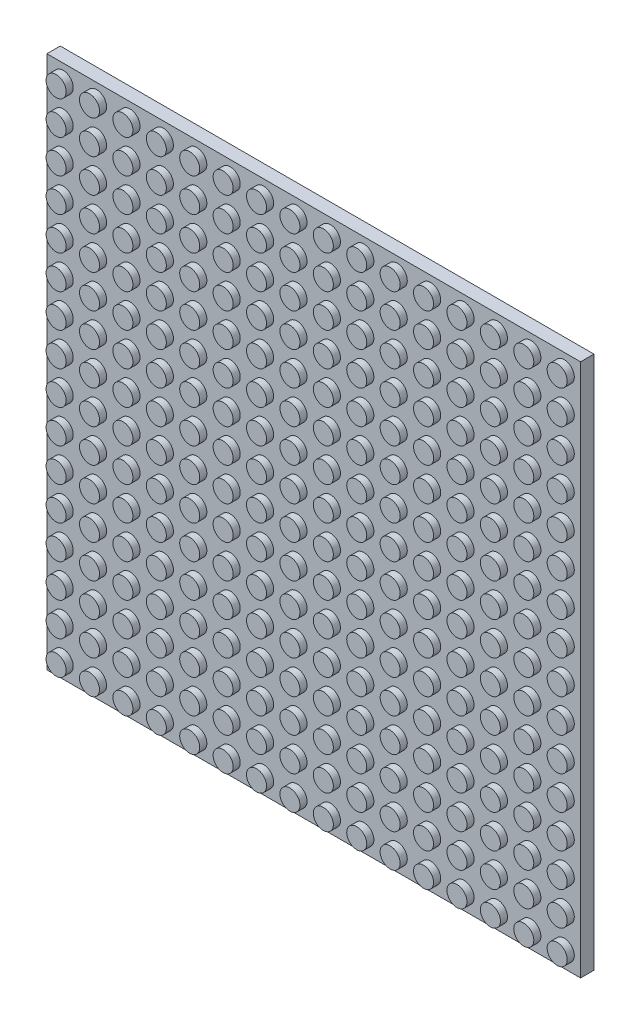
SolidWorks part; units mm, degrees
ref_plane "Спереди" through (0, 0, 0) normal (0, 0, 1) x (1, 0, 0)
ref_plane "Сверху" through (0, 0, 0) normal (0, 1, 0) x (1, 0, 0)
ref_plane "Справа" through (0, 0, 0) normal (1, 0, 0) x (0, 0, -1)
sketch "Эскиз1" plane through (0, 0, 0) normal (0, 0, 1) x (1, 0, 0)
  line L1 (-63.9, -63.9) -> (63.9, -63.9)
  line L2 (-63.9, -63.9) -> (-63.9, 63.9)
  line L3 (-63.9, 63.9) -> (63.9, 63.9)
  line L4 (63.9, -63.9) -> (63.9, 63.9)
  line L5 (-63.9, -63.9) -> (63.9, 63.9) construction
  line L6 (-63.9, 63.9) -> (63.9, -63.9) construction
  point P0 (0, 0)
  dimension "D1" = 127.8
  dimension "D2" = 127.8
extrude "Бобышка-Вытянуть1" add sketch "Эскиз1" along normal blind 3.2
sketch "Эскиз2" plane through (0, 0, 3.2) normal (0, 0, 1) x (1, 0, 0)
  line L0 (-63.9, 63.9) -> (-63.9, -63.9) construction
  line L1 (63.9, 63.9) -> (-63.9, 63.9) construction
  circle A0 centre (-60, 60) radius 2.4
  circle A1 centre (-52, 60) radius 2.4
  circle A2 centre (-44, 60) radius 2.4
  circle A3 centre (-36, 60) radius 2.4
  circle A4 centre (-28, 60) radius 2.4
  circle A5 centre (-20, 60) radius 2.4
  circle A6 centre (-12, 60) radius 2.4
  circle A7 centre (-4, 60) radius 2.4
  circle A8 centre (4, 60) radius 2.4
  circle A9 centre (12, 60) radius 2.4
  circle A10 centre (20, 60) radius 2.4
  circle A11 centre (28, 60) radius 2.4
  circle A12 centre (36, 60) radius 2.4
  circle A13 centre (44, 60) radius 2.4
  circle A14 centre (52, 60) radius 2.4
  circle A15 centre (60, 60) radius 2.4
  circle A16 centre (-52, 52) radius 2.4
  circle A17 centre (-44, 52) radius 2.4
  circle A18 centre (-36, 52) radius 2.4
  circle A19 centre (-28, 52) radius 2.4
  circle A20 centre (-20, 52) radius 2.4
  circle A21 centre (-12, 52) radius 2.4
  circle A22 centre (-4, 52) radius 2.4
  circle A23 centre (4, 52) radius 2.4
  circle A24 centre (12, 52) radius 2.4
  circle A25 centre (20, 52) radius 2.4
  circle A26 centre (28, 52) radius 2.4
  circle A27 centre (36, 52) radius 2.4
  circle A28 centre (44, 52) radius 2.4
  circle A29 centre (52, 52) radius 2.4
  circle A30 centre (60, 52) radius 2.4
  circle A31 centre (-52, 44) radius 2.4
  circle A32 centre (-44, 44) radius 2.4
  circle A33 centre (-36, 44) radius 2.4
  circle A34 centre (-28, 44) radius 2.4
  circle A35 centre (-20, 44) radius 2.4
  circle A36 centre (-12, 44) radius 2.4
  circle A37 centre (-4, 44) radius 2.4
  circle A38 centre (4, 44) radius 2.4
  circle A39 centre (12, 44) radius 2.4
  circle A40 centre (20, 44) radius 2.4
  circle A41 centre (28, 44) radius 2.4
  circle A42 centre (36, 44) radius 2.4
  circle A43 centre (44, 44) radius 2.4
  circle A44 centre (52, 44) radius 2.4
  circle A45 centre (60, 44) radius 2.4
  circle A46 centre (-52, 36) radius 2.4
  circle A47 centre (-44, 36) radius 2.4
  circle A48 centre (-36, 36) radius 2.4
  circle A49 centre (-28, 36) radius 2.4
  circle A50 centre (-20, 36) radius 2.4
  circle A51 centre (-12, 36) radius 2.4
  circle A52 centre (-4, 36) radius 2.4
  circle A53 centre (4, 36) radius 2.4
  circle A54 centre (12, 36) radius 2.4
  circle A55 centre (20, 36) radius 2.4
  circle A56 centre (28, 36) radius 2.4
  circle A57 centre (36, 36) radius 2.4
  circle A58 centre (44, 36) radius 2.4
  circle A59 centre (52, 36) radius 2.4
  circle A60 centre (60, 36) radius 2.4
  circle A61 centre (-52, 28) radius 2.4
  circle A62 centre (-44, 28) radius 2.4
  circle A63 centre (-36, 28) radius 2.4
  circle A64 centre (-28, 28) radius 2.4
  circle A65 centre (-20, 28) radius 2.4
  circle A66 centre (-12, 28) radius 2.4
  circle A67 centre (-4, 28) radius 2.4
  circle A68 centre (4, 28) radius 2.4
  circle A69 centre (12, 28) radius 2.4
  circle A70 centre (20, 28) radius 2.4
  circle A71 centre (28, 28) radius 2.4
  circle A72 centre (36, 28) radius 2.4
  circle A73 centre (44, 28) radius 2.4
  circle A74 centre (52, 28) radius 2.4
  circle A75 centre (60, 28) radius 2.4
  circle A76 centre (-52, 20) radius 2.4
  circle A77 centre (-44, 20) radius 2.4
  circle A78 centre (-36, 20) radius 2.4
  circle A79 centre (-28, 20) radius 2.4
  circle A80 centre (-20, 20) radius 2.4
  circle A81 centre (-12, 20) radius 2.4
  circle A82 centre (-4, 20) radius 2.4
  circle A83 centre (4, 20) radius 2.4
  circle A84 centre (12, 20) radius 2.4
  circle A85 centre (20, 20) radius 2.4
  circle A86 centre (28, 20) radius 2.4
  circle A87 centre (36, 20) radius 2.4
  circle A88 centre (44, 20) radius 2.4
  circle A89 centre (52, 20) radius 2.4
  circle A90 centre (60, 20) radius 2.4
  circle A91 centre (-52, 12) radius 2.4
  circle A92 centre (-44, 12) radius 2.4
  circle A93 centre (-36, 12) radius 2.4
  circle A94 centre (-28, 12) radius 2.4
  circle A95 centre (-20, 12) radius 2.4
  circle A96 centre (-12, 12) radius 2.4
  circle A97 centre (-4, 12) radius 2.4
  circle A98 centre (4, 12) radius 2.4
  circle A99 centre (12, 12) radius 2.4
  circle A100 centre (20, 12) radius 2.4
  circle A101 centre (28, 12) radius 2.4
  circle A102 centre (36, 12) radius 2.4
  circle A103 centre (44, 12) radius 2.4
  circle A104 centre (52, 12) radius 2.4
  circle A105 centre (60, 12) radius 2.4
  circle A106 centre (-52, 4) radius 2.4
  circle A107 centre (-44, 4) radius 2.4
  circle A108 centre (-36, 4) radius 2.4
  circle A109 centre (-28, 4) radius 2.4
  circle A110 centre (-20, 4) radius 2.4
  circle A111 centre (-12, 4) radius 2.4
  circle A112 centre (-4, 4) radius 2.4
  circle A113 centre (4, 4) radius 2.4
  circle A114 centre (12, 4) radius 2.4
  circle A115 centre (20, 4) radius 2.4
  circle A116 centre (28, 4) radius 2.4
  circle A117 centre (36, 4) radius 2.4
  circle A118 centre (44, 4) radius 2.4
  circle A119 centre (52, 4) radius 2.4
  circle A120 centre (60, 4) radius 2.4
  circle A121 centre (-52, -4) radius 2.4
  circle A122 centre (-44, -4) radius 2.4
  circle A123 centre (-36, -4) radius 2.4
  circle A124 centre (-28, -4) radius 2.4
  circle A125 centre (-20, -4) radius 2.4
  circle A126 centre (-12, -4) radius 2.4
  circle A127 centre (-4, -4) radius 2.4
  circle A128 centre (4, -4) radius 2.4
  circle A129 centre (12, -4) radius 2.4
  circle A130 centre (20, -4) radius 2.4
  circle A131 centre (28, -4) radius 2.4
  circle A132 centre (36, -4) radius 2.4
  circle A133 centre (44, -4) radius 2.4
  circle A134 centre (52, -4) radius 2.4
  circle A135 centre (60, -4) radius 2.4
  circle A136 centre (-52, -12) radius 2.4
  circle A137 centre (-44, -12) radius 2.4
  circle A138 centre (-36, -12) radius 2.4
  circle A139 centre (-28, -12) radius 2.4
  circle A140 centre (-20, -12) radius 2.4
  circle A141 centre (-12, -12) radius 2.4
  circle A142 centre (-4, -12) radius 2.4
  circle A143 centre (4, -12) radius 2.4
  circle A144 centre (12, -12) radius 2.4
  circle A145 centre (20, -12) radius 2.4
  circle A146 centre (28, -12) radius 2.4
  circle A147 centre (36, -12) radius 2.4
  circle A148 centre (44, -12) radius 2.4
  circle A149 centre (52, -12) radius 2.4
  circle A150 centre (60, -12) radius 2.4
  circle A151 centre (-52, -20) radius 2.4
  circle A152 centre (-44, -20) radius 2.4
  circle A153 centre (-36, -20) radius 2.4
  circle A154 centre (-28, -20) radius 2.4
  circle A155 centre (-20, -20) radius 2.4
  circle A156 centre (-12, -20) radius 2.4
  circle A157 centre (-4, -20) radius 2.4
  circle A158 centre (4, -20) radius 2.4
  circle A159 centre (12, -20) radius 2.4
  circle A160 centre (20, -20) radius 2.4
  circle A161 centre (28, -20) radius 2.4
  circle A162 centre (36, -20) radius 2.4
  circle A163 centre (44, -20) radius 2.4
  circle A164 centre (52, -20) radius 2.4
  circle A165 centre (60, -20) radius 2.4
  circle A166 centre (-52, -28) radius 2.4
  circle A167 centre (-44, -28) radius 2.4
  circle A168 centre (-36, -28) radius 2.4
  circle A169 centre (-28, -28) radius 2.4
  circle A170 centre (-20, -28) radius 2.4
  circle A171 centre (-12, -28) radius 2.4
  circle A172 centre (-4, -28) radius 2.4
  circle A173 centre (4, -28) radius 2.4
  circle A174 centre (12, -28) radius 2.4
  circle A175 centre (20, -28) radius 2.4
  circle A176 centre (28, -28) radius 2.4
  circle A177 centre (36, -28) radius 2.4
  circle A178 centre (44, -28) radius 2.4
  circle A179 centre (52, -28) radius 2.4
  circle A180 centre (60, -28) radius 2.4
  circle A181 centre (-52, -36) radius 2.4
  circle A182 centre (-44, -36) radius 2.4
  circle A183 centre (-36, -36) radius 2.4
  circle A184 centre (-28, -36) radius 2.4
  circle A185 centre (-20, -36) radius 2.4
  circle A186 centre (-12, -36) radius 2.4
  circle A187 centre (-4, -36) radius 2.4
  circle A188 centre (4, -36) radius 2.4
  circle A189 centre (12, -36) radius 2.4
  circle A190 centre (20, -36) radius 2.4
  circle A191 centre (28, -36) radius 2.4
  circle A192 centre (36, -36) radius 2.4
  circle A193 centre (44, -36) radius 2.4
  circle A194 centre (52, -36) radius 2.4
  circle A195 centre (60, -36) radius 2.4
  circle A196 centre (-52, -44) radius 2.4
  circle A197 centre (-44, -44) radius 2.4
  circle A198 centre (-36, -44) radius 2.4
  circle A199 centre (-28, -44) radius 2.4
  circle A200 centre (-20, -44) radius 2.4
  circle A201 centre (-12, -44) radius 2.4
  circle A202 centre (-4, -44) radius 2.4
  circle A203 centre (4, -44) radius 2.4
  circle A204 centre (12, -44) radius 2.4
  circle A205 centre (20, -44) radius 2.4
  circle A206 centre (28, -44) radius 2.4
  circle A207 centre (36, -44) radius 2.4
  circle A208 centre (44, -44) radius 2.4
  circle A209 centre (52, -44) radius 2.4
  circle A210 centre (60, -44) radius 2.4
  circle A211 centre (-52, -52) radius 2.4
  circle A212 centre (-44, -52) radius 2.4
  circle A213 centre (-36, -52) radius 2.4
  circle A214 centre (-28, -52) radius 2.4
  circle A215 centre (-20, -52) radius 2.4
  circle A216 centre (-12, -52) radius 2.4
  circle A217 centre (-4, -52) radius 2.4
  circle A218 centre (4, -52) radius 2.4
  circle A219 centre (12, -52) radius 2.4
  circle A220 centre (20, -52) radius 2.4
  circle A221 centre (28, -52) radius 2.4
  circle A222 centre (36, -52) radius 2.4
  circle A223 centre (44, -52) radius 2.4
  circle A224 centre (52, -52) radius 2.4
  circle A225 centre (60, -52) radius 2.4
  circle A226 centre (-52, -60) radius 2.4
  circle A227 centre (-44, -60) radius 2.4
  circle A228 centre (-36, -60) radius 2.4
  circle A229 centre (-28, -60) radius 2.4
  circle A230 centre (-20, -60) radius 2.4
  circle A231 centre (-12, -60) radius 2.4
  circle A232 centre (-4, -60) radius 2.4
  circle A233 centre (4, -60) radius 2.4
  circle A234 centre (12, -60) radius 2.4
  circle A235 centre (20, -60) radius 2.4
  circle A236 centre (28, -60) radius 2.4
  circle A237 centre (36, -60) radius 2.4
  circle A238 centre (44, -60) radius 2.4
  circle A239 centre (52, -60) radius 2.4
  circle A240 centre (60, -60) radius 2.4
  circle A241 centre (-60, 52) radius 2.4
  circle A242 centre (-60, 44) radius 2.4
  circle A243 centre (-60, 36) radius 2.4
  circle A244 centre (-60, 28) radius 2.4
  circle A245 centre (-60, 20) radius 2.4
  circle A246 centre (-60, 12) radius 2.4
  circle A247 centre (-60, 4) radius 2.4
  circle A248 centre (-60, -4) radius 2.4
  circle A249 centre (-60, -12) radius 2.4
  circle A250 centre (-60, -20) radius 2.4
  circle A251 centre (-60, -28) radius 2.4
  circle A252 centre (-60, -36) radius 2.4
  circle A253 centre (-60, -44) radius 2.4
  circle A254 centre (-60, -52) radius 2.4
  circle A255 centre (-60, -60) radius 2.4
  dimension "D1" = 3.9
  dimension "D2" = 3.9
  dimension "D3" = 16
extrude "Бобышка-Вытянуть2" add sketch "Эскиз2" along normal blind 1.7
sketch "Эскиз5" plane through (0, 0, 0) normal (0, 0, -1) x (-1, 0, 0)
  line L0 (-63.9, 63.9) -> (63.9, 63.9) construction
  line L1 (-63.9, -63.9) -> (-63.9, 63.9) construction
  circle A0 centre (-60, 60) radius 2.5
  circle A1 centre (-52, 60) radius 2.5
  circle A2 centre (-44, 60) radius 2.5
  circle A3 centre (-36, 60) radius 2.5
  circle A4 centre (-28, 60) radius 2.5
  circle A5 centre (-20, 60) radius 2.5
  circle A6 centre (-12, 60) radius 2.5
  circle A7 centre (-4, 60) radius 2.5
  circle A8 centre (4, 60) radius 2.5
  circle A9 centre (12, 60) radius 2.5
  circle A10 centre (20, 60) radius 2.5
  circle A11 centre (28, 60) radius 2.5
  circle A12 centre (36, 60) radius 2.5
  circle A13 centre (44, 60) radius 2.5
  circle A14 centre (52, 60) radius 2.5
  circle A15 centre (60, 60) radius 2.5
  circle A16 centre (-52, 52) radius 2.5
  circle A17 centre (-44, 52) radius 2.5
  circle A18 centre (-36, 52) radius 2.5
  circle A19 centre (-28, 52) radius 2.5
  circle A20 centre (-20, 52) radius 2.5
  circle A21 centre (-12, 52) radius 2.5
  circle A22 centre (-4, 52) radius 2.5
  circle A23 centre (4, 52) radius 2.5
  circle A24 centre (12, 52) radius 2.5
  circle A25 centre (20, 52) radius 2.5
  circle A26 centre (28, 52) radius 2.5
  circle A27 centre (36, 52) radius 2.5
  circle A28 centre (44, 52) radius 2.5
  circle A29 centre (52, 52) radius 2.5
  circle A30 centre (60, 52) radius 2.5
  circle A31 centre (-52, 44) radius 2.5
  circle A32 centre (-44, 44) radius 2.5
  circle A33 centre (-36, 44) radius 2.5
  circle A34 centre (-28, 44) radius 2.5
  circle A35 centre (-20, 44) radius 2.5
  circle A36 centre (-12, 44) radius 2.5
  circle A37 centre (-4, 44) radius 2.5
  circle A38 centre (4, 44) radius 2.5
  circle A39 centre (12, 44) radius 2.5
  circle A40 centre (20, 44) radius 2.5
  circle A41 centre (28, 44) radius 2.5
  circle A42 centre (36, 44) radius 2.5
  circle A43 centre (44, 44) radius 2.5
  circle A44 centre (52, 44) radius 2.5
  circle A45 centre (60, 44) radius 2.5
  circle A46 centre (-52, 36) radius 2.5
  circle A47 centre (-44, 36) radius 2.5
  circle A48 centre (-36, 36) radius 2.5
  circle A49 centre (-28, 36) radius 2.5
  circle A50 centre (-20, 36) radius 2.5
  circle A51 centre (-12, 36) radius 2.5
  circle A52 centre (-4, 36) radius 2.5
  circle A53 centre (4, 36) radius 2.5
  circle A54 centre (12, 36) radius 2.5
  circle A55 centre (20, 36) radius 2.5
  circle A56 centre (28, 36) radius 2.5
  circle A57 centre (36, 36) radius 2.5
  circle A58 centre (44, 36) radius 2.5
  circle A59 centre (52, 36) radius 2.5
  circle A60 centre (60, 36) radius 2.5
  circle A61 centre (-52, 28) radius 2.5
  circle A62 centre (-44, 28) radius 2.5
  circle A63 centre (-36, 28) radius 2.5
  circle A64 centre (-28, 28) radius 2.5
  circle A65 centre (-20, 28) radius 2.5
  circle A66 centre (-12, 28) radius 2.5
  circle A67 centre (-4, 28) radius 2.5
  circle A68 centre (4, 28) radius 2.5
  circle A69 centre (12, 28) radius 2.5
  circle A70 centre (20, 28) radius 2.5
  circle A71 centre (28, 28) radius 2.5
  circle A72 centre (36, 28) radius 2.5
  circle A73 centre (44, 28) radius 2.5
  circle A74 centre (52, 28) radius 2.5
  circle A75 centre (60, 28) radius 2.5
  circle A76 centre (-52, 20) radius 2.5
  circle A77 centre (-44, 20) radius 2.5
  circle A78 centre (-36, 20) radius 2.5
  circle A79 centre (-28, 20) radius 2.5
  circle A80 centre (-20, 20) radius 2.5
  circle A81 centre (-12, 20) radius 2.5
  circle A82 centre (-4, 20) radius 2.5
  circle A83 centre (4, 20) radius 2.5
  circle A84 centre (12, 20) radius 2.5
  circle A85 centre (20, 20) radius 2.5
  circle A86 centre (28, 20) radius 2.5
  circle A87 centre (36, 20) radius 2.5
  circle A88 centre (44, 20) radius 2.5
  circle A89 centre (52, 20) radius 2.5
  circle A90 centre (60, 20) radius 2.5
  circle A91 centre (-52, 12) radius 2.5
  circle A92 centre (-44, 12) radius 2.5
  circle A93 centre (-36, 12) radius 2.5
  circle A94 centre (-28, 12) radius 2.5
  circle A95 centre (-20, 12) radius 2.5
  circle A96 centre (-12, 12) radius 2.5
  circle A97 centre (-4, 12) radius 2.5
  circle A98 centre (4, 12) radius 2.5
  circle A99 centre (12, 12) radius 2.5
  circle A100 centre (20, 12) radius 2.5
  circle A101 centre (28, 12) radius 2.5
  circle A102 centre (36, 12) radius 2.5
  circle A103 centre (44, 12) radius 2.5
  circle A104 centre (52, 12) radius 2.5
  circle A105 centre (60, 12) radius 2.5
  circle A106 centre (-52, 4) radius 2.5
  circle A107 centre (-44, 4) radius 2.5
  circle A108 centre (-36, 4) radius 2.5
  circle A109 centre (-28, 4) radius 2.5
  circle A110 centre (-20, 4) radius 2.5
  circle A111 centre (-12, 4) radius 2.5
  circle A112 centre (-4, 4) radius 2.5
  circle A113 centre (4, 4) radius 2.5
  circle A114 centre (12, 4) radius 2.5
  circle A115 centre (20, 4) radius 2.5
  circle A116 centre (28, 4) radius 2.5
  circle A117 centre (36, 4) radius 2.5
  circle A118 centre (44, 4) radius 2.5
  circle A119 centre (52, 4) radius 2.5
  circle A120 centre (60, 4) radius 2.5
  circle A121 centre (-52, -4) radius 2.5
  circle A122 centre (-44, -4) radius 2.5
  circle A123 centre (-36, -4) radius 2.5
  circle A124 centre (-28, -4) radius 2.5
  circle A125 centre (-20, -4) radius 2.5
  circle A126 centre (-12, -4) radius 2.5
  circle A127 centre (-4, -4) radius 2.5
  circle A128 centre (4, -4) radius 2.5
  circle A129 centre (12, -4) radius 2.5
  circle A130 centre (20, -4) radius 2.5
  circle A131 centre (28, -4) radius 2.5
  circle A132 centre (36, -4) radius 2.5
  circle A133 centre (44, -4) radius 2.5
  circle A134 centre (52, -4) radius 2.5
  circle A135 centre (60, -4) radius 2.5
  circle A136 centre (-52, -12) radius 2.5
  circle A137 centre (-44, -12) radius 2.5
  circle A138 centre (-36, -12) radius 2.5
  circle A139 centre (-28, -12) radius 2.5
  circle A140 centre (-20, -12) radius 2.5
  circle A141 centre (-12, -12) radius 2.5
  circle A142 centre (-4, -12) radius 2.5
  circle A143 centre (4, -12) radius 2.5
  circle A144 centre (12, -12) radius 2.5
  circle A145 centre (20, -12) radius 2.5
  circle A146 centre (28, -12) radius 2.5
  circle A147 centre (36, -12) radius 2.5
  circle A148 centre (44, -12) radius 2.5
  circle A149 centre (52, -12) radius 2.5
  circle A150 centre (60, -12) radius 2.5
  circle A151 centre (-52, -20) radius 2.5
  circle A152 centre (-44, -20) radius 2.5
  circle A153 centre (-36, -20) radius 2.5
  circle A154 centre (-28, -20) radius 2.5
  circle A155 centre (-20, -20) radius 2.5
  circle A156 centre (-12, -20) radius 2.5
  circle A157 centre (-4, -20) radius 2.5
  circle A158 centre (4, -20) radius 2.5
  circle A159 centre (12, -20) radius 2.5
  circle A160 centre (20, -20) radius 2.5
  circle A161 centre (28, -20) radius 2.5
  circle A162 centre (36, -20) radius 2.5
  circle A163 centre (44, -20) radius 2.5
  circle A164 centre (52, -20) radius 2.5
  circle A165 centre (60, -20) radius 2.5
  circle A166 centre (-52, -28) radius 2.5
  circle A167 centre (-44, -28) radius 2.5
  circle A168 centre (-36, -28) radius 2.5
  circle A169 centre (-28, -28) radius 2.5
  circle A170 centre (-20, -28) radius 2.5
  circle A171 centre (-12, -28) radius 2.5
  circle A172 centre (-4, -28) radius 2.5
  circle A173 centre (4, -28) radius 2.5
  circle A174 centre (12, -28) radius 2.5
  circle A175 centre (20, -28) radius 2.5
  circle A176 centre (28, -28) radius 2.5
  circle A177 centre (36, -28) radius 2.5
  circle A178 centre (44, -28) radius 2.5
  circle A179 centre (52, -28) radius 2.5
  circle A180 centre (60, -28) radius 2.5
  circle A181 centre (-52, -36) radius 2.5
  circle A182 centre (-44, -36) radius 2.5
  circle A183 centre (-36, -36) radius 2.5
  circle A184 centre (-28, -36) radius 2.5
  circle A185 centre (-20, -36) radius 2.5
  circle A186 centre (-12, -36) radius 2.5
  circle A187 centre (-4, -36) radius 2.5
  circle A188 centre (4, -36) radius 2.5
  circle A189 centre (12, -36) radius 2.5
  circle A190 centre (20, -36) radius 2.5
  circle A191 centre (28, -36) radius 2.5
  circle A192 centre (36, -36) radius 2.5
  circle A193 centre (44, -36) radius 2.5
  circle A194 centre (52, -36) radius 2.5
  circle A195 centre (60, -36) radius 2.5
  circle A196 centre (-52, -44) radius 2.5
  circle A197 centre (-44, -44) radius 2.5
  circle A198 centre (-36, -44) radius 2.5
  circle A199 centre (-28, -44) radius 2.5
  circle A200 centre (-20, -44) radius 2.5
  circle A201 centre (-12, -44) radius 2.5
  circle A202 centre (-4, -44) radius 2.5
  circle A203 centre (4, -44) radius 2.5
  circle A204 centre (12, -44) radius 2.5
  circle A205 centre (20, -44) radius 2.5
  circle A206 centre (28, -44) radius 2.5
  circle A207 centre (36, -44) radius 2.5
  circle A208 centre (44, -44) radius 2.5
  circle A209 centre (52, -44) radius 2.5
  circle A210 centre (60, -44) radius 2.5
  circle A211 centre (-52, -52) radius 2.5
  circle A212 centre (-44, -52) radius 2.5
  circle A213 centre (-36, -52) radius 2.5
  circle A214 centre (-28, -52) radius 2.5
  circle A215 centre (-20, -52) radius 2.5
  circle A216 centre (-12, -52) radius 2.5
  circle A217 centre (-4, -52) radius 2.5
  circle A218 centre (4, -52) radius 2.5
  circle A219 centre (12, -52) radius 2.5
  circle A220 centre (20, -52) radius 2.5
  circle A221 centre (28, -52) radius 2.5
  circle A222 centre (36, -52) radius 2.5
  circle A223 centre (44, -52) radius 2.5
  circle A224 centre (52, -52) radius 2.5
  circle A225 centre (60, -52) radius 2.5
  circle A226 centre (-52, -60) radius 2.5
  circle A227 centre (-44, -60) radius 2.5
  circle A228 centre (-36, -60) radius 2.5
  circle A229 centre (-28, -60) radius 2.5
  circle A230 centre (-20, -60) radius 2.5
  circle A231 centre (-12, -60) radius 2.5
  circle A232 centre (-4, -60) radius 2.5
  circle A233 centre (4, -60) radius 2.5
  circle A234 centre (12, -60) radius 2.5
  circle A235 centre (20, -60) radius 2.5
  circle A236 centre (28, -60) radius 2.5
  circle A237 centre (36, -60) radius 2.5
  circle A238 centre (44, -60) radius 2.5
  circle A239 centre (52, -60) radius 2.5
  circle A240 centre (60, -60) radius 2.5
  circle A241 centre (-60, 52) radius 2.5
  circle A242 centre (-60, 44) radius 2.5
  circle A243 centre (-60, 36) radius 2.5
  circle A244 centre (-60, 28) radius 2.5
  circle A245 centre (-60, 20) radius 2.5
  circle A246 centre (-60, 12) radius 2.5
  circle A247 centre (-60, 4) radius 2.5
  circle A248 centre (-60, -4) radius 2.5
  circle A249 centre (-60, -12) radius 2.5
  circle A250 centre (-60, -20) radius 2.5
  circle A251 centre (-60, -28) radius 2.5
  circle A252 centre (-60, -36) radius 2.5
  circle A253 centre (-60, -44) radius 2.5
  circle A254 centre (-60, -52) radius 2.5
  circle A255 centre (-60, -60) radius 2.5
  dimension "D1" = 3.9
  dimension "D3" = 16
  dimension "D2" = 3.9
extrude "Вырез-Вытянуть1" cut sketch "Эскиз5" against normal blind 1.8
